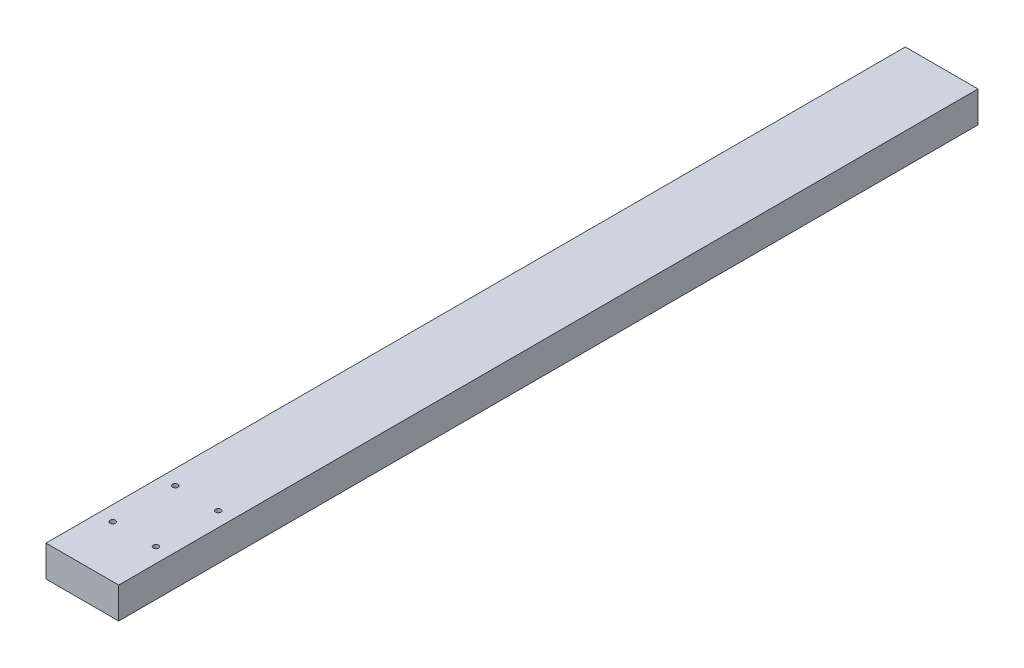
SolidWorks part; units mm, degrees
material "Pine"
ref_plane "Front Plane" through (0, 0, 0) normal (0, 0, 1) x (1, 0, 0)
ref_plane "Top Plane" through (0, 0, 0) normal (0, 1, 0) x (1, 0, 0)
ref_plane "Right Plane" through (0, 0, 0) normal (1, 0, 0) x (0, 0, -1)
sketch "Sketch1" plane through (0, 0, 0) normal (0, 0, 1) x (1, 0, 0)
  line L1 (-44.45, -19.05) -> (44.45, -19.05)
  line L2 (-44.45, -19.05) -> (-44.45, 19.05)
  line L3 (-44.45, 19.05) -> (44.45, 19.05)
  line L4 (44.45, -19.05) -> (44.45, 19.05)
  line L5 (-44.45, -19.05) -> (44.45, 19.05) construction
  line L6 (-44.45, 19.05) -> (44.45, -19.05) construction
  point P0 (0, 0)
  dimension "D1" = 88.9
  dimension "D2" = 38.1
extrude "Boss-Extrude1" add sketch "Sketch1" along normal blind 1050.8
sketch "Sketch2" plane through (0, 19.05, 0) normal (0, 1, 0) x (1, 0, 0)
  line L0 (44.45, -987.3) -> (-44.45, -987.3) construction
  line L1 (44.45, -1050.8) -> (44.45, 0) construction
  line L2 (-44.45, -1050.8) -> (-44.45, 0) construction
  line L3 (44.45, -911.1) -> (-44.45, -911.1) construction
  line L4 (44.45, -1050.8) -> (-44.45, -1050.8) construction
  line L5 (0, -987.3) -> (0, -911.1) construction
  circle A0 centre (26.5491, -987.3) radius 3.25
  circle A1 centre (-26.2169, -987.3) radius 3.25
  circle A2 centre (26.5491, -911.1) radius 3.25
  circle A3 centre (-26.2169, -911.1) radius 3.25
  dimension "D3" = 6.5
  dimension "D1" = 63.5
  dimension "D2" = 76.2
extrude "Cut-Extrude1" cut sketch "Sketch2" against normal up to next
